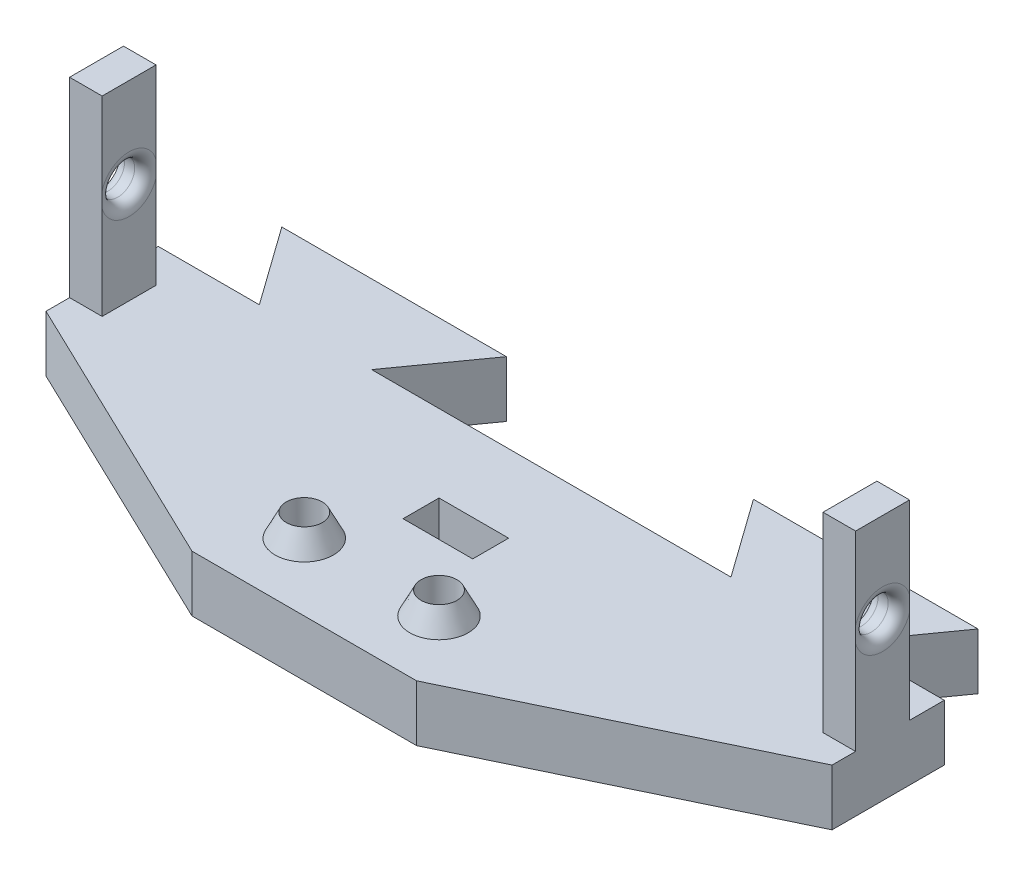
SolidWorks part; units mm, degrees
ref_plane "Front Plane" through (0, 0, 0) normal (0, 0, 1) x (1, 0, 0)
ref_plane "Top Plane" through (0, 0, 0) normal (0, 1, 0) x (1, 0, 0)
ref_plane "Right Plane" through (0, 0, 0) normal (1, 0, 0) x (0, 0, -1)
sketch "Sketch1" plane through (0, 0, 0) normal (0, 1, 0) x (1, 0, 0)
  line L0 (0, 0) -> (20, 0)
  line L1 (10, 0) -> (10, 12) construction
  line L2 (10, 12) -> (-25, 12) construction
  line L3 (0, 0) -> (-25, 12)
  line L4 (-25, 12) -> (-25, 22)
  line L5 (-25, 22) -> (45, 22)
  line L6 (45, 22) -> (45, 12)
  line L7 (45, 12) -> (20, 0)
  dimension "D1" = 35
  dimension "D2" = 20
  dimension "D3" = 12
  dimension "D4" = 70
  dimension "D5" = 10
  dimension "D6" = 10
extrude "Boss-Extrude1" add sketch "Sketch1" along normal blind 5
sketch "Sketch2" plane through (0, 5, 0) normal (0, 1, 0) x (1, 0, 0)
  line L0 (10, 0) -> (10, 22) construction
  line L1 (0, 0) -> (20, 0) construction
  line L2 (45, 22) -> (-25, 22) construction
  circle A0 centre (4, 6) radius 1.6
  circle A1 centre (16, 6) radius 1.6
  dimension "D1" = 3.2
  dimension "D2" = 6
  dimension "D3" = 6
extrude "Cut-Extrude1" cut sketch "Sketch2" against normal blind 3
ref_plane "Plane1" through (0, 0, -6) normal (0, 0, 1) x (1, 0, 0)
sketch "Sketch6" plane through (0, 0, -6) normal (0, 0, 1) x (1, 0, 0)
  line L0 (2.4, 5) -> (2.4, 7)
  line L1 (2.4, 7) -> (1.4, 5)
  line L2 (1.4, 5) -> (2.4, 5)
  line L3 (2.4, 5) -> (5.6, 5) construction
  line L4 (4, 5) -> (4, 7.7373) construction
  dimension "D1" = 2
  dimension "D2" = 1
revolve "Revolve1" add sketch "Sketch6" angle 360 about L4
sketch "Sketch7" plane through (0, 0, -6) normal (0, 0, 1) x (1, 0, 0)
  line L0 (14.4, 5) -> (14.4, 7)
  line L1 (14.4, 7) -> (13.4, 5)
  line L2 (13.4, 5) -> (14.4, 5)
  line L3 (14.4, 5) -> (17.6, 5) construction
  line L4 (16, 5) -> (16, 8.947) construction
  dimension "D1" = 2
  dimension "D2" = 1
revolve "Revolve2" add sketch "Sketch7" angle 360 about L4
sketch "Sketch9" plane through (0, 5, 0) normal (0, 1, 0) x (1, 0, 0)
  line L0 (10, 0) -> (10, 22) construction
  line L1 (0, 0) -> (20, 0) construction
  line L2 (45, 22) -> (-25, 22) construction
  line L3 (10, 11.9) -> (-25, 11.9) construction
  line L4 (-25, 22) -> (-25, 12) construction
  line L5 (-2.75, 6) -> (2.75, 6) construction
  line L7 (6.9, 11.9) -> (13.1, 11.9)
  line L8 (6.9, 11.9) -> (6.9, 15.1)
  line L9 (6.9, 15.1) -> (13.1, 15.1)
  line L10 (13.1, 11.9) -> (13.1, 15.1)
  dimension "D1" = 5.9
  dimension "D2" = 3.1
  dimension "D3" = 3.1
  dimension "D4" = 3.2
sketch "Sketch10" plane through (0, 5, 0) normal (0, 1, 0) x (1, 0, 0)
  line L0 (-25, 22) -> (-25, 12) construction
  line L1 (-25, 18.9) -> (-22.1, 18.9)
  line L2 (-25, 18.9) -> (-25, 14.1)
  line L3 (-25, 14.1) -> (-22.1, 14.1)
  line L4 (-22.1, 18.9) -> (-22.1, 14.1)
  line L5 (45, 22) -> (-25, 22) construction
  line L6 (10, 22) -> (10, 0) construction
  line L7 (0, 0) -> (20, 0) construction
  line L8 (45, 14.1) -> (42.1, 14.1)
  line L9 (42.1, 18.9) -> (42.1, 14.1)
  line L10 (45, 18.9) -> (42.1, 18.9)
  line L11 (45, 18.9) -> (45, 14.1)
  dimension "D1" = 3.1
  dimension "D2" = 4.8
  dimension "D3" = 2.9
extrude "Boss-Extrude2" add sketch "Sketch10" along normal blind 17
extrude "Cut-Extrude4" cut sketch "Sketch9" against normal blind 5
sketch "Sketch11" plane through (-25, 0, 0) normal (-1, 0, 0) x (0, 0, 1)
  circle A0 centre (-16.5, 14) radius 1.5
  dimension "D1" = 3
  dimension "D2" = 9
extrude "Cut-Extrude5" cut sketch "Sketch11" against normal blind 70
fillet "Fillet3" radius 1 1 edges at (-25, 14, -15)
fillet "Fillet4" radius 1 1 edges at (-22.1, 14, -15)
fillet "Fillet6" radius 1 1 edges at (42.1, 14, -18)
fillet "Fillet7" radius 1 1 edges at (45, 14, -15)
sketch "Sketch13" plane through (0, 5, 0) normal (0, 1, 0) x (1, 0, 0)
  line L0 (-16, 22) -> (-21, 29)
  line L1 (45, 22) -> (-25, 22) construction
  line L2 (-21, 29) -> (-1, 29)
  line L3 (-1, 29) -> (-6, 22)
  line L4 (10, 22) -> (10, 29) construction
  line L5 (21, 29) -> (26, 22)
  line L6 (41, 29) -> (21, 29)
  line L7 (36, 22) -> (41, 29)
  line L8 (-16, 22) -> (-6, 22)
  line L9 (26, 22) -> (36, 22)
  point P13 (0, 0)
  dimension "D1" = 5
  dimension "D2" = 4
  dimension "D3" = 10
  dimension "D4" = 5
  dimension "D5" = 7
extrude "Boss-Extrude4" add sketch "Sketch13" against normal blind 5
